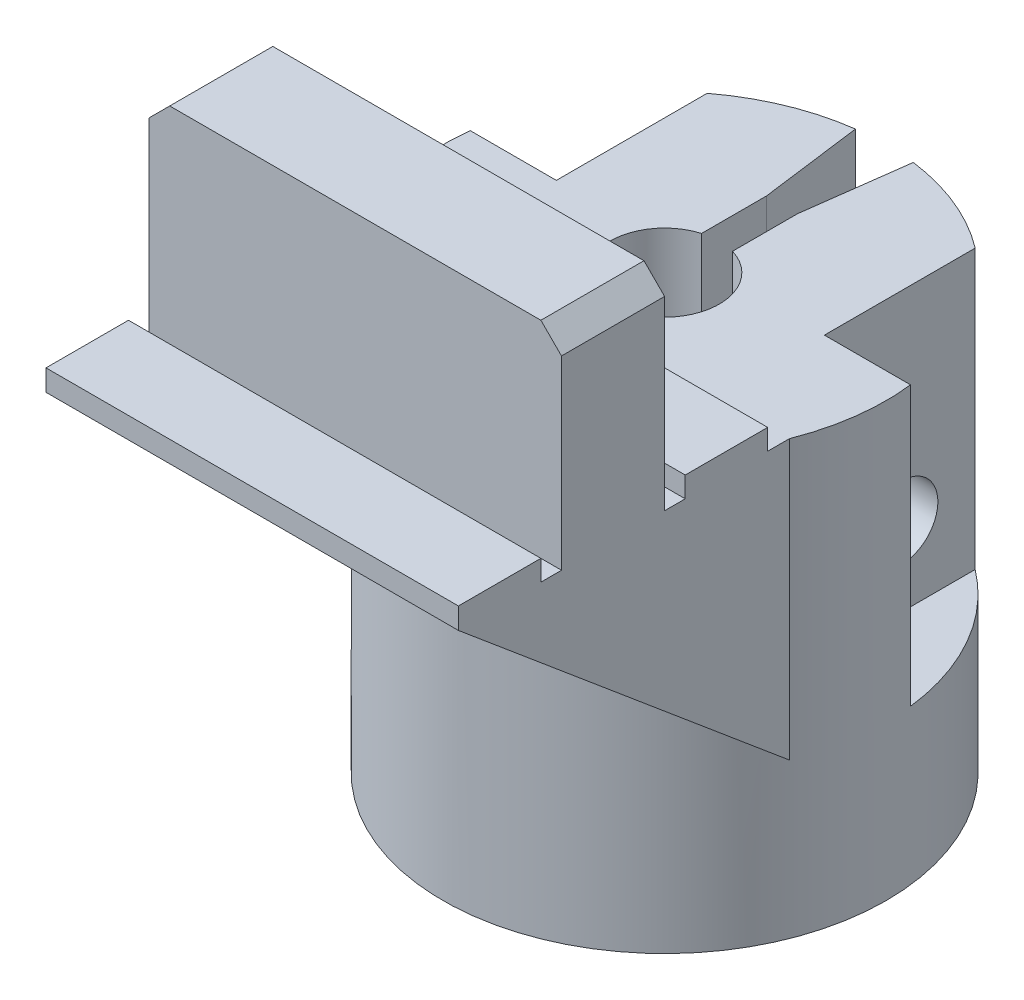
SolidWorks part; units mm, degrees
ref_plane "Přední rovina" through (0, 0, 0) normal (0, 0, 1) x (1, 0, 0)
ref_plane "Horní rovina" through (0, 0, 0) normal (0, 1, 0) x (1, 0, 0)
ref_plane "Pravá rovina" through (0, 0, 0) normal (1, 0, 0) x (0, 0, -1)
sketch "Skica1" plane through (0, 0, 0) normal (0, 1, 0) x (1, 0, 0)
  line L0 (5, 6.5) -> (-5, 6.5) construction
  line L1 (5, 8.25) -> (8, 8.25) construction
  line L2 (5, 8.25) -> (5, 1.75) construction
  line L3 (5, 1.75) -> (8, 1.75) construction
  line L4 (8, 8.25) -> (8, 1.75) construction
  line L5 (-5, 6.5) -> (-5, 3.5) construction
  line L6 (-5, 3.5) -> (5, 3.5) construction
  line L7 (-5, 5) -> (5, 5) construction
  line L8 (-7.5, 8.25) -> (-5, 8.25) construction
  line L9 (-7.5, 8.25) -> (-7.5, 1.75) construction
  line L10 (-7.5, 1.75) -> (-5, 1.75) construction
  line L11 (-5, 8.25) -> (-5, 1.75) construction
  line L13 (-7.75, 6.5877) -> (-7.75, 3.4123) construction
  line L14 (-7.75, 3.4123) -> (-5, 1.8246) construction
  line L15 (-5, 1.8246) -> (-2.25, 3.4123) construction
  line L16 (-2.25, 3.4123) -> (-2.25, 6.5877) construction
  line L17 (-2.25, 6.5877) -> (-5, 8.1754) construction
  line L18 (-5, 8.1754) -> (-7.75, 6.5877) construction
  circle A0 centre (0, 0) radius 2.5 construction
  circle A1 centre (0, 0) radius 2.65
  circle A2 centre (0, 0) radius 10.75
  circle A3 centre (-5, 5) radius 2.75 construction
  point P11 (5, 5)
  point P14 (-5, 5)
  point P15 (-5, 5)
  point P25 (0, 6.5)
  dimension "D1" = 5
  dimension "D2" = 0.15
  dimension "D3" = 5.3
  dimension "D4" = 21.5
  dimension "D5" = 6.5
  dimension "D6" = 3
  dimension "D7" = 3
  dimension "D8" = 6.5
  dimension "D9" = 2.5
  dimension "D10" = 5
  dimension "D11" = 10
  dimension "D12" = 5.5
extrude "Přidat vysunutím1" add sketch "Skica1" along normal blind 21
sketch "Skica2" plane through (0, 21, 0) normal (0, 1, 0) x (1, 0, 0)
  line L1 (-0.75, 10.75) -> (0.75, 10.75)
  line L2 (-0.75, 10.75) -> (-0.75, -4)
  line L3 (-0.75, -4) -> (0.75, -4)
  line L4 (0.75, 10.75) -> (0.75, -4)
  circle A0 centre (0, 0) radius 10.75 construction
  point P4 (0, -4)
  dimension "D1" = 1.5
  dimension "D2" = 4
extrude "Odebrat vysunutím1" cut sketch "Skica2" against normal through all and the other way through all
sketch "Skica4" plane through (0, 21, 0) normal (0, 1, 0) x (1, 0, 0)
  line L0 (-10.6771, 1.25) -> (-6.5, 1.25)
  line L1 (-6.5, 1.25) -> (-6.5, 8.5623)
  line L2 (6.5, 8.5623) -> (6.5, 1.25)
  line L3 (6.5, 1.25) -> (10.6771, 1.25)
  line L4 (-7.5, 1.75) -> (-5, 1.75) construction
  circle A0 centre (0, 0) radius 10.75 construction
  circle A1 centre (0, 0) radius 10.75
  arc M6 (-0.75, 10.7238) -> (0.75, 10.7238) centre (0, 0) ccw
  dimension "D1" = 13
  dimension "D2" = 0.5
extrude "Odebrat vysunutím2" cut sketch "Skica4" against normal offset from surface (13.5 mm away) 7.5 contours L0 L1 M6 | L3 A1 L2 region at (-8.1328, 21, -4.023) region at (8.1328, 21, -4.023) up to face at (0, 0, 1.0033)
sketch "Skica5" plane through (-6.5, 0, 0) normal (-1, 0, 0) x (0, 0, 1)
  line L1 (-1.25, 7.5) -> (-8.5623, 7.5) construction
  line L2 (-5, 8.0746) -> (-2.25, 9.6623) construction
  line L3 (-2.25, 9.6623) -> (-2.25, 12.8377) construction
  line L4 (-2.25, 12.8377) -> (-5, 14.4254) construction
  line L5 (-5, 14.4254) -> (-7.75, 12.8377) construction
  line L6 (-7.75, 12.8377) -> (-7.75, 9.6623) construction
  line L7 (-7.75, 9.6623) -> (-5, 8.0746) construction
  circle A0 centre (-5, 11.25) radius 1.75
  circle A1 centre (-5, 11.25) radius 3.25 construction
  circle A2 centre (-5, 11.25) radius 2.75 construction
  dimension "D1" = 3.5
  dimension "D2" = 6.5
  dimension "D3" = 5.5
  dimension "D4" = 3.75
extrude "Odebrat vysunutím3" cut sketch "Skica5" against normal through all
sketch "Skica10" plane through (0, 21, 0) normal (0, 1, 0) x (1, 0, 0)
  line L0 (-10, -3.9449) -> (10, -3.9449)
  arc A0 (-10.6771, 1.25) -> (10.6771, 1.25) centre (0, 0) ccw construction
  dimension "D1" = 20
sketch "Skica6" plane through (0, 0, 0) normal (1, 0, 0) x (0, 0, -1)
  line L0 (-15, 31) -> (-10, 31)
  line L1 (-10, 31) -> (-10, 21)
  line L2 (-15, 31) -> (-15, 16.7763)
  line L3 (-15, 16.7763) -> (-3.9449, 7.5)
  line L4 (-10, 21) -> (-3.9449, 21)
  line L5 (-3.9449, 21) -> (-3.9449, 7.5)
  line L6 (1.25, 21) -> (-10.75, 21) construction
  line L9 (8.5623, 7.5) -> (1.25, 7.5) construction
  line L10 (-10.75, 0) -> (10.7238, 0) construction
  dimension "D1" = 5
  dimension "D2" = 10
  dimension "D3" = 10
  dimension "D4" = 40
extrude "Přidat vysunutím3" add sketch "Skica6" along normal mid plane 20 contours L0 L1 L4 L5 L3 L2
extrude "Odebrat vysunutím4" cut sketch "Skica2<2>" against normal through all
sketch "Skica2<2>" plane through (0, 21, 0) normal (0, 1, 0) x (1, 0, 0) same geometry as "Skica2"
sketch "Skica8" plane through (10, 0, 0) normal (1, 0, 0) x (0, 0, -1)
  line L0 (-15, 16.7763) -> (-17.5734, 18.9357)
  line L1 (-17.5734, 18.9357) -> (-17.5734, 21)
  line L2 (-17.5734, 21) -> (-15, 21)
  line L3 (-15, 31) -> (-15, 16.7763) construction
  line L4 (-10, 21) -> (-3.9449, 21) construction
  line L5 (-15, 16.7763) -> (-3.9449, 7.5) construction
  line L6 (-15, 21) -> (-15, 16.7763)
extrude "Přidat vysunutím6" add sketch "Skica8" against normal up to surface (20 mm away) contours L0 L1 L2 L6 up to face at (-10, 21.3794, 9.6483)
chamfer "Zkosení1" distance 1 angle 45 2 edges at (-10, 31, 12.5) (10, 31, 12.5)
sketch "Skica9" plane through (0, 21, 0) normal (0, 1, 0) x (1, 0, 0)
  line L0 (10, -10) -> (10, -3.9449) construction
  line L1 (-10, -17.5734) -> (10, -17.5734)
  line L2 (-10, -17.5734) -> (-10, -15)
  line L3 (-10, -15) -> (10, -15)
  line L4 (10, -17.5734) -> (10, -15)
  line L5 (-10, -10) -> (10, -10)
  line L6 (-10, -10) -> (-10, -5)
  line L7 (-10, -5) -> (10, -5)
  line L8 (10, -10) -> (10, -5)
  dimension "D1" = 5
extrude "Přidat vysunutím5" add sketch "Skica9" along normal blind 1
sketch "Skica11" plane through (0, 21, 0) normal (0, 1, 0) x (1, 0, 0)
  line L0 (10, -5) -> (-10, -5) construction
  line L1 (-0.75, -4) -> (0.75, -4)
  line L2 (-0.75, -4) -> (-0.75, -5)
  line L3 (-0.75, -5) -> (0.75, -5)
  line L4 (0.75, -4) -> (0.75, -5)
extrude "Odebrat vysunutím5" cut sketch "Skica11" against normal through all
sketch "Skica12" plane through (0, 21, 0) normal (0, 1, 0) x (1, 0, 0)
  line L0 (0, 0) -> (-1.4153, 10.75)
  line L1 (-1.4153, 10.75) -> (1.4153, 10.75)
  line L2 (1.4153, 10.75) -> (0, 0)
  arc A0 (-0.75, 10.7238) -> (-6.5, 8.5623) centre (0, 0) ccw construction
  point P3 (0, 10.75)
  dimension "D1" = 15
extrude "Odebrat vysunutím6" cut sketch "Skica12" against normal through all
sketch "Skica13" plane through (10, 0, 0) normal (1, 0, 0) x (0, 0, -1)
  line L0 (-17.5734, 18.9357) -> (-20, 20.9718)
  line L1 (-20, 20.9718) -> (-20, 22)
  line L2 (-20, 22) -> (-17.5734, 22)
  line L3 (-17.5734, 22) -> (-17.5734, 18.9357)
  line L4 (-17.5734, 22) -> (-15, 22) construction
  line L5 (-15, 30) -> (-15, 22) construction
  line L6 (-17.5734, 18.9357) -> (-3.9449, 7.5) construction
  point P3 (-17.5734, 19.025)
  point P6 (-17.5734, 22)
  dimension "D1" = 5
extrude "Přidat vysunutím7" add sketch "Skica13" against normal up to surface (20 mm away) up to face at (-10, 21.6436, 10.3037)
sketch "Skica15" plane through (-10, 0, 0) normal (-1, 0, 0) x (0, 0, 1)
  line L1 (10, 22) -> (9, 22)
  line L2 (10, 22) -> (10, 21)
  line L3 (10, 21) -> (9, 21)
  line L4 (9, 22) -> (9, 21)
  line L5 (15, 22) -> (16, 22)
  line L6 (15, 22) -> (15, 21)
  line L7 (15, 21) -> (16, 21)
  line L8 (16, 22) -> (16, 21)
  dimension "D1" = 1
  dimension "D2" = 1
extrude "Odebrat vysunutím8" cut sketch "Skica15" against normal through all
